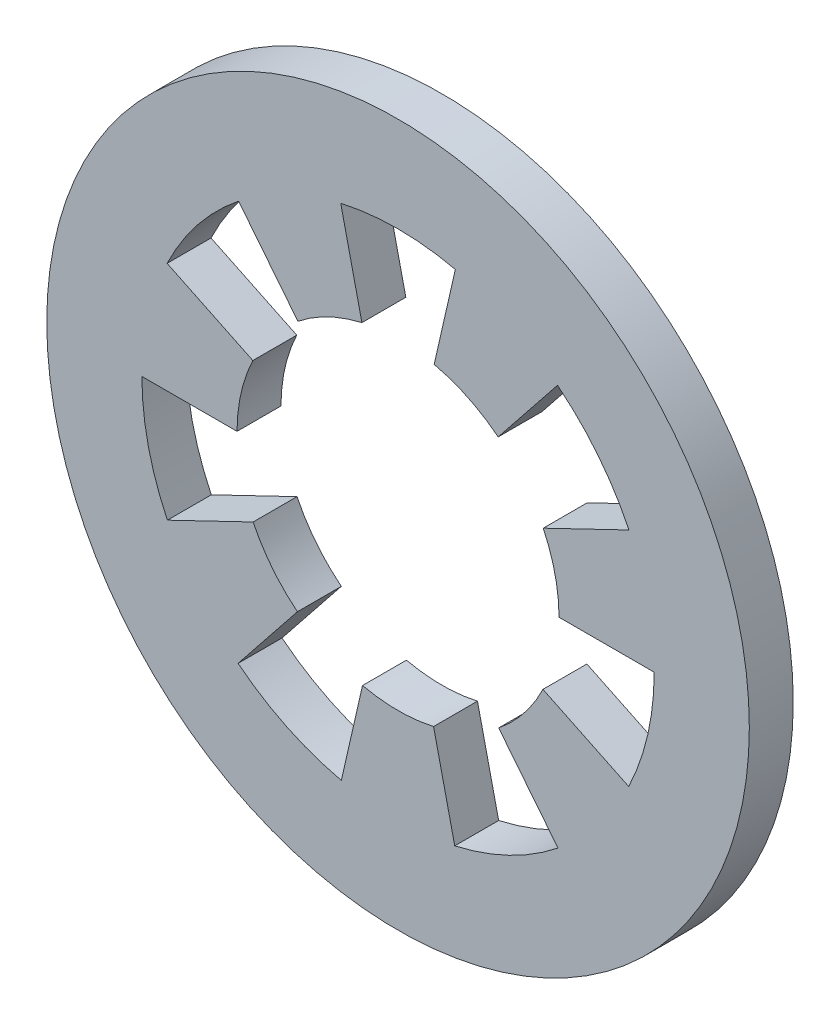
SolidWorks part; units mm, degrees
ref_plane "Front Plane" through (0, 0, 0) normal (0, 0, 1) x (1, 0, 0)
ref_plane "Top Plane" through (0, 0, 0) normal (0, 1, 0) x (1, 0, 0)
ref_plane "Right Plane" through (0, 0, 0) normal (1, 0, 0) x (0, 0, -1)
sketch "BodySke" plane through (0, 0, 0) normal (0, 1, 0) x (1, 0, 0)
  line L0 (0, 0) -> (0, 7) construction
  line L2 (1.1, 0) -> (2.4, 0)
  line L3 (1.1, 0) -> (1.1, 0.3)
  line L4 (1.1, 0.3) -> (2.4, 0.3)
  line L5 (2.4, 0) -> (2.4, 0.3)
revolve "BaseBody" add sketch "BodySke" angle 360 about L0
sketch "ToothSke" plane through (0, 0, 0) normal (0, 0, 1) x (1, 0, 0)
  line L0 (0, 0) -> (0, 2.7341) construction
  line L2 (-0.3915, 1.7057) -> (-0.2468, 1.0719)
  line L3 (-0.2468, 1.0719) -> (0.2468, 1.0719)
  line L4 (0.3915, 1.7057) -> (0.2468, 1.0719)
  circle A0 centre (0, 0) radius 1.75 construction
  arc A1 (-0.3915, 1.7057) -> (0.3915, 1.7057) centre (0, 0) cw
  circle A2 centre (0, 0) radius 1.1 construction
  circle A3 centre (0, 0) radius 1.1 construction
  point P11 (0, 1.0719)
  point P12 (0, 1.75)
  dimension "D1" = 3.5
  dimension "D2" = 0.4937
  dimension "D3" = 25.714
extrude "ToothCut" cut sketch "ToothSke" against normal through all
pattern_circular "ToothPat" count 7 over 360 about axis through (0, 0, 0) along (0, 0, -1) of "ToothCut"
equation "\"D1@ToothSke\" =  ( \"Inner_dia@BodySke\" + \"Outer_dia@BodySke\" )  / 2"
equation "\"D2@ToothSke\" =  pi  * \"Inner_dia@BodySke\" / 2 / \"Num_tooth@BodySke\""
equation "\"D3@ToothSke\" = 180 / \"Num_tooth@BodySke\""
equation "\"Num_tooth@ToothPat\" = \"Num_tooth@BodySke\""
